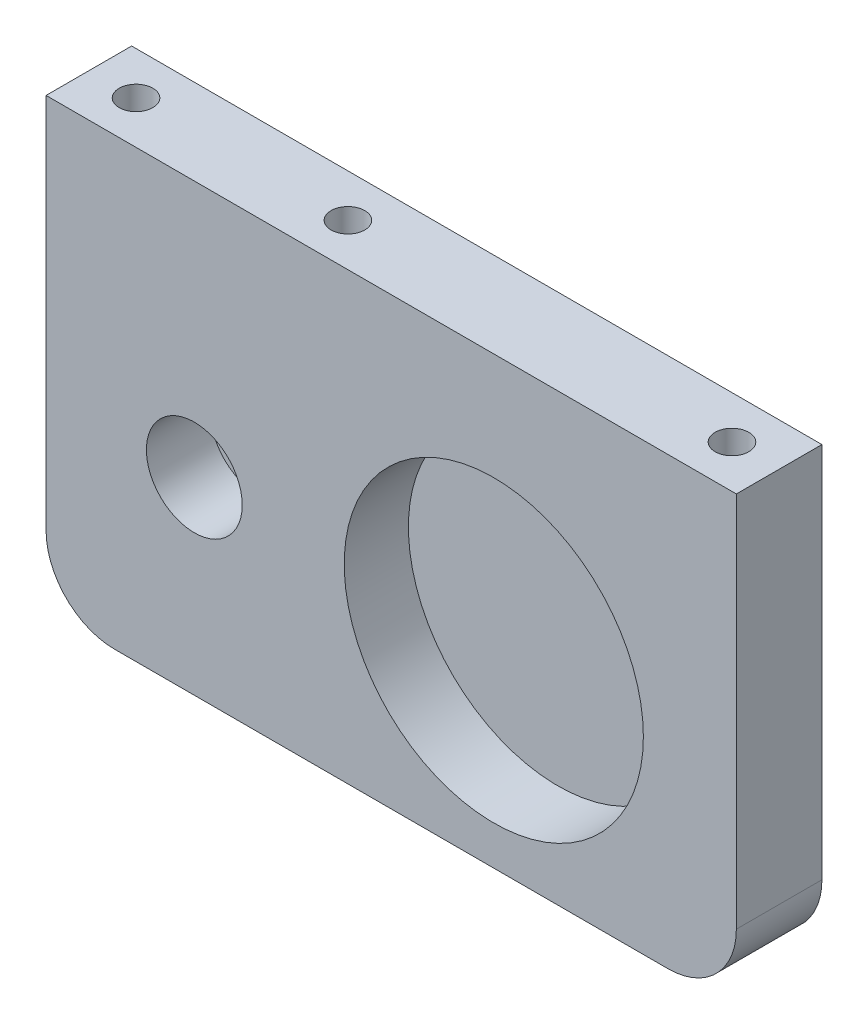
SolidWorks part; units mm, degrees
ref_plane "Front Plane" through (0, 0, 0) normal (0, 0, 1) x (1, 0, 0)
ref_plane "Top Plane" through (0, 0, 0) normal (0, 1, 0) x (1, 0, 0)
ref_plane "Right Plane" through (0, 0, 0) normal (1, 0, 0) x (0, 0, -1)
sketch "Sketch1" plane through (0, 0, 0) normal (0, 0, 1) x (1, 0, 0)
  line L10 (-33.225, 19.05) -> (18, 19.05)
  line L11 (-33.225, 19.05) -> (-33.225, -14)
  line L12 (-33.225, -14) -> (18, -14)
  line L13 (18, 19.05) -> (18, -14)
  circle A2 centre (0, 0) radius 11.1 construction
  circle A3 centre (-22.225, 0) radius 3.556 construction
  dimension "D2" = 7.112
  dimension "D5" = 19.05
  dimension "D6" = 11
  dimension "D3" = 22.225
  dimension "D1" = 22.2
  dimension "D8" = 51.225
  dimension "D4" = 14
  dimension "D7" = 18
extrude "Boss-Extrude1" add sketch "Sketch1" against normal blind 6.35
sketch "Sketch8" plane through (0, 19.05, 0) normal (0, 1, 0) x (1, 0, 0)
  line L0 (-33.225, 3.175) -> (18, 3.175) construction
  line L1 (-33.225, 6.35) -> (-33.225, 0) construction
  line L2 (18, 6.35) -> (18, 0) construction
  circle A1 centre (-29.725, 3.175) radius 1.25
  circle A2 centre (-14, 3.175) radius 1.25
  circle A3 centre (14.5, 3.175) radius 1.25
  dimension "D1" = 2.5
  dimension "D2" = 3.5
  dimension "D3" = 3.5
  dimension "D4" = 14
extrude "Cut-Extrude4" cut sketch "Sketch8" against normal blind 15
fillet "Fillet3" radius 5.08 2 edges at (18, -14, -3.175) (-33.225, -14, -3.175)
sketch "Sketch10" plane through (0, 0, 0) normal (0, 0, 1) x (1, 0, 0)
  circle A0 centre (-22.225, 0) radius 3.556 construction
  circle A1 centre (0, 0) radius 11.1 construction
  circle A2 centre (-22.225, 0) radius 3.556
  circle A3 centre (0, 0) radius 11.1
extrude "Cut-Extrude5" cut sketch "Sketch10" against normal offset from surface (4.7625 mm away) 1.5875 up to face at (-7.6125, -1.6407, -6.35)
